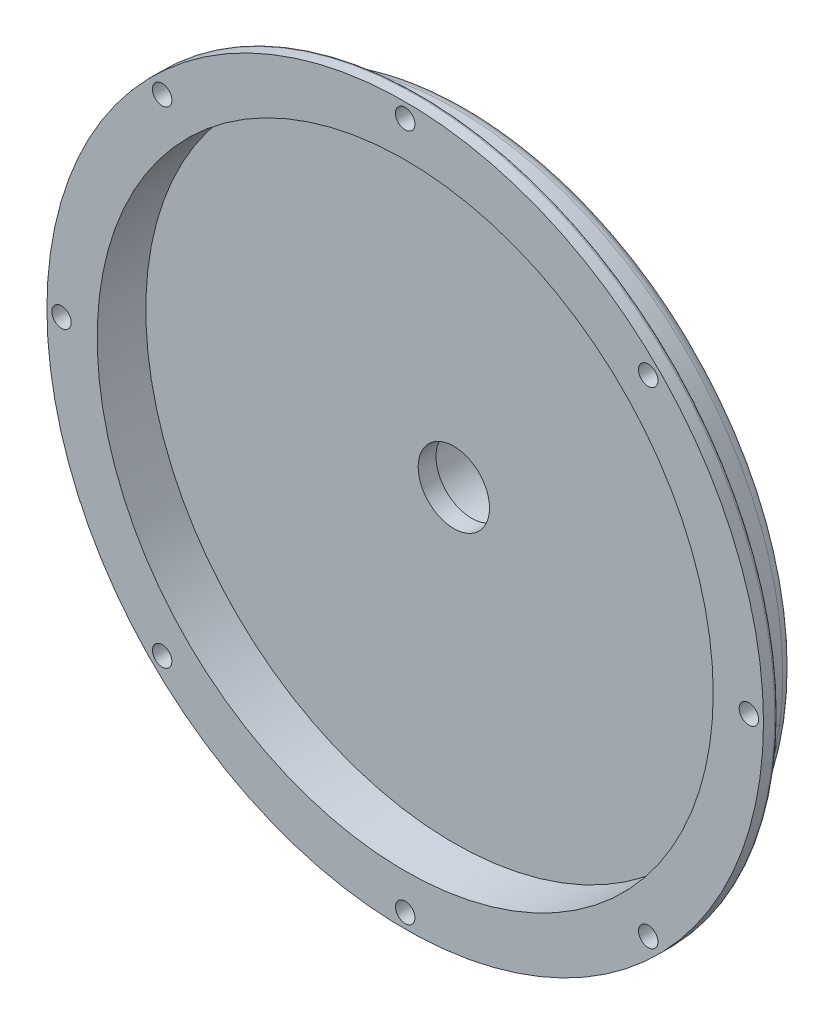
SolidWorks part; units mm, degrees
ref_plane "Спереди" through (0, 0, 0) normal (0, 0, 1) x (1, 0, 0)
ref_plane "Сверху" through (0, 0, 0) normal (0, 1, 0) x (1, 0, 0)
ref_plane "Справа" through (0, 0, 0) normal (1, 0, 0) x (0, 0, -1)
sketch "Эскиз1" plane through (0, 0, 0) normal (0, 1, 0) x (1, 0, 0)
  line L0 (0, 0) -> (-110.5, 0) construction
  line L3 (0, 0) -> (0, 56.2194) construction
  line L4 (0, 25.5) -> (-26.5, 25.5)
  line L5 (-110.5, 0) -> (0, 0)
  line L6 (-26.5, 25.5) -> (-26.5, 22.5)
  line L7 (-96.6379, 19.5) -> (-29.5, 19.5)
  line L8 (0, 0) -> (0, 25.5)
  line L18 (-96.6379, 19.5) -> (-38, 19.5) construction
  line L19 (-101.4661, 5.4194) -> (-100.6249, 15.8224) construction
  line L21 (-101.5, 5) -> (-101.5, 19.5) construction
  line L22 (-109.5, 4.5) -> (-102.4628, 4.5) construction
  line L23 (-110.5, 0) -> (-110.5, 3.5)
  line L24 (-102.4628, 4.5) -> (-109.5, 4.5)
  line L25 (-101.4661, 5.4194) -> (-100.6249, 15.8224)
  arc A5 (-100.6249, 15.8224) -> (-96.6379, 19.5) centre (-96.6379, 15.5) cw construction
  arc A6 (-110.5, 3.5) -> (-109.5, 4.5) centre (-109.5, 3.5) cw construction
  arc A7 (-102.4628, 4.5) -> (-101.4661, 5.4194) centre (-102.4628, 5.5) ccw construction
  arc A8 (-110.5, 3.5) -> (-109.5, 4.5) centre (-109.5, 3.5) cw
  arc A9 (-101.4661, 5.4194) -> (-102.4628, 4.5) centre (-102.4628, 5.5) cw
  arc A10 (-100.6249, 15.8224) -> (-96.6379, 19.5) centre (-96.6379, 15.5) cw
  arc A11 (-26.5, 22.5) -> (-29.5, 19.5) centre (-29.5, 22.5) cw
  point P9 (-26.5, 19.5)
  point P39 (-100.3276, 19)
  point P44 (-110.5, 4.5)
  dimension "D8" = 4.5
  dimension "D9" = 15
  dimension "D3" = 1
  dimension "D4" = 1
  dimension "D5" = 4
  dimension "D7" = 3
  dimension "D1" = 110.5
  dimension "D2" = 26.5
  dimension "D6" = 6
sketch "Эскиз2" plane through (0, 0, 0) normal (0, 0, 1) x (1, 0, 0)
  circle A0 centre (0, 0) radius 106 construction
  circle A1 centre (0, 106) radius 3
  circle A2 centre (74.9533, 74.9533) radius 3
  circle A3 centre (106, 0) radius 3
  circle A4 centre (74.9533, -74.9533) radius 3
  circle A5 centre (0, -106) radius 3
  circle A6 centre (-74.9533, -74.9533) radius 3
  circle A7 centre (-106, 0) radius 3
  circle A8 centre (-74.9533, 74.9533) radius 3
  point P22 (0, 0)
  dimension "D1" = 212
  dimension "D2" = 6
  dimension "D3" = 8
revolve "Повернуть1" add sketch "Эскиз1" angle 360 about L8
extrude "Вырез-Вытянуть1" cut sketch "Эскиз2" against normal blind 10
sketch "Эскиз3" plane through (0, 0, -25.5) normal (0, 0, 1) x (1, 0, 0)
  circle A0 centre (0, 0) radius 15
  dimension "D1" = 30
extrude "Вырез-Вытянуть2" cut sketch "Эскиз3" along normal blind 5
sketch "Эскиз7" plane through (0, 0, -25.5) normal (0, 0, -1) x (-1, 0, 0)
  circle A0 centre (0, 0) radius 17
  circle A1 centre (0, 0) radius 15
  dimension "D1" = 34
  dimension "D2" = 30
extrude "Бобышка-Вытянуть1" add sketch "Эскиз7" along normal blind 14.5
sketch "Эскиз5" plane through (0, 0, 0) normal (0, 0, 1) x (1, 0, 0)
  circle A0 centre (0, 0) radius 95
  dimension "D1" = 190
extrude "Вырез-Вытянуть4" cut sketch "Эскиз5" against normal blind 15
sketch "Эскиз6" plane through (0, 0, -20.5) normal (0, 0, -1) x (-1, 0, 0)
  circle A0 centre (0, 0) radius 11
  dimension "D1" = 22
extrude "Вырез-Вытянуть5" cut sketch "Эскиз6" against normal blind 15
fillet "Скругление1" radius 1 1 edges at (26.5, 0, -25.5)
sketch "Эскиз10" plane through (0, 0, -40) normal (0, 0, -1) x (-1, 0, 0)
  circle A0 centre (0, 0) radius 17.75
  circle A1 centre (0, 0) radius 15.5
  point P4 (0, 0)
  point P5 (0, 0)
  dimension "D1" = 35.5
  dimension "D2" = 31
extrude "Бобышка-Вытянуть2" add sketch "Эскиз10" against normal blind 13
sketch "Эскиз11" plane through (0, 0, 0) normal (1, 0, 0) x (0, 0, -1)
  line L0 (40.5255, 17.7825) -> (40.1603, 17.15)
  line L1 (39.6407, 17.15) -> (39.2755, 17.7825)
  line L2 (39.2755, 17.7825) -> (39.2755, 18.652)
  line L3 (39.2755, 18.652) -> (40.5255, 18.652)
  line L4 (40.5255, 18.652) -> (40.5255, 17.7825)
  line L5 (39.2755, 17.7825) -> (40.5255, 17.7825) construction
  line L6 (46.1144, 0) -> (29.6728, 0) construction
  arc A0 (40.1603, 17.15) -> (39.6407, 17.15) centre (39.9005, 17.3) cw
  point P2 (0, 0)
  point P11 (39.9005, 16.7)
  point P13 (39.9005, 17)
  dimension "D4" = 0.3
  dimension "D1" = 1.25
  dimension "D2" = 60
  dimension "D3" = 17
sketch "Эскиз12" plane through (0, 0, 0) normal (1, 0, 0) x (0, 0, -1)
  line L0 (40.6858, 0) -> (27, 0)
  line L1 (46.1144, 0) -> (29.6728, 0) construction
  line L2 (27, 17) -> (27, -17) construction
sketch "Эскиз14" plane through (0, 0, -40) normal (0, 0, -1) x (-1, 0, 0)
  circle A0 centre (0, 0) radius 17
curve "Спираль1" pitch 1 height 13 turns 13
sweep "Вырез-По траектории1" [suppressed] cut profiles "Эскиз11" path "Спираль1"
sketch "Эскиз15" plane through (0, 0, 0) normal (1, 0, 0) x (0, 0, -1)
  line L0 (38.7746, 18.0359) -> (40.5629, 15.4911)
  line L1 (40.5629, 15.4911) -> (42.1448, 15.4911)
  line L2 (42.1448, 15.4911) -> (42.1448, 19.3427)
  line L3 (42.1448, 19.3427) -> (38.7746, 19.3427)
  line L4 (38.7746, 19.3427) -> (38.7746, 18.0359)
revolve "Вырез-Повернуть1" cut sketch "Эскиз15" angle 360 about L0
